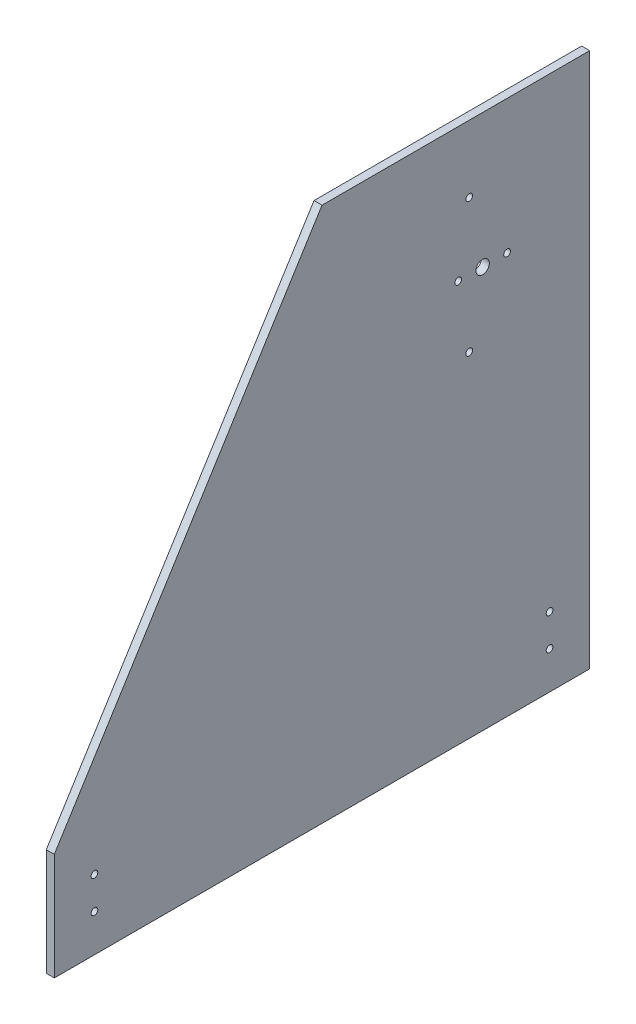
SolidWorks part; units mm, degrees
ref_plane "Front Plane" through (0, 0, 0) normal (0, 0, 1) x (1, 0, 0)
ref_plane "Top Plane" through (0, 0, 0) normal (0, 1, 0) x (1, 0, 0)
ref_plane "Right Plane" through (0, 0, 0) normal (1, 0, 0) x (0, 0, -1)
sketch "Sketch1" plane through (0, 0, 0) normal (1, 0, 0) x (0, 0, -1)
  line L0 (0, -2343.7616) -> (0, 114844.3172) construction
  line L1 (-2343.7616, 0) -> (114844.3172, 0) construction
  line L2 (0, 80) -> (400, 80) construction
  line L3 (0, 0) -> (400, 0)
  line L5 (200, 400) -> (400, 400)
  line L6 (400, 0) -> (400, 400)
  line L7 (0, 80) -> (200, 400)
  line L8 (0, 80) -> (0, 0)
  line L9 (-1000, 40) -> (49000, 40) construction
  line L10 (200, -1000) -> (200, 49000) construction
  line L11 (310, -1000) -> (310, 49000) construction
  line L12 (320, -1008.4066) -> (320, 48991.5934) construction
  line L13 (301.75, 300) -> (338.25, 300) construction
  circle A0 centre (30, 52) radius 2.5
  circle A2 centre (30, 28) radius 2.5
  circle A3 centre (370, 28) radius 2.5
  circle A4 centre (370, 52) radius 2.5
  circle A5 centre (310, 350) radius 2.5
  circle A6 centre (310, 250) radius 2.5
  circle A7 centre (320, 300) radius 5
  circle A8 centre (338.25, 300) radius 2.5
  circle A9 centre (301.75, 300) radius 2.5
  point P14 (0, 40)
  point P21 (200, 0)
  point P38 (320, 300)
  dimension "D7" = 5
  dimension "D9" = 5
  dimension "D14" = 10
  dimension "D16" = 36.5
  dimension "D17" = 5
  dimension "D15" = 5
  dimension "D1" = 400
  dimension "D2" = 400
  dimension "D3" = 80
  dimension "D4" = 200
  dimension "D5" = 30
  dimension "D6" = 90
  dimension "D8" = 12
  dimension "D10" = 50
  dimension "D11" = 100
  dimension "D12" = 80
  dimension "D13" = 50
extrude "Boss-Extrude1" add sketch "Sketch1" along normal blind 6
